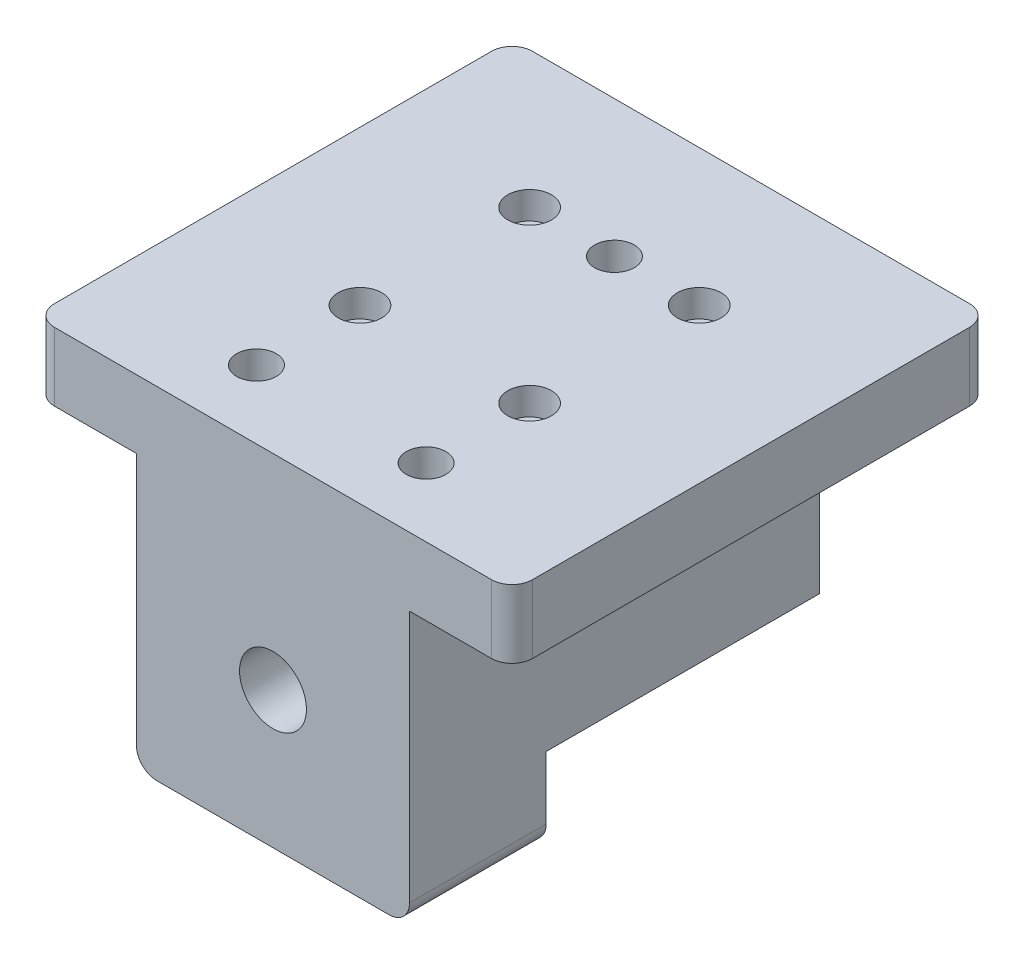
SolidWorks part; units mm, degrees
ref_plane "Front Plane" through (0, 0, 0) normal (0, 0, 1) x (1, 0, 0)
ref_plane "Top Plane" through (0, 0, 0) normal (0, 1, 0) x (1, 0, 0)
ref_plane "Right Plane" through (0, 0, 0) normal (1, 0, 0) x (0, 0, -1)
sketch "Sketch1" plane through (0, 0, 0) normal (0, 0, 1) x (1, 0, 0)
  line L0 (4.222, -2.1267) -> (4.222, 1.8147)
  line L1 (4.7961, 3.2006) -> (6.7433, 5.1479)
  line L2 (6.9512, 5.234) -> (8.142, 5.234)
  line L3 (8.436, 4.94) -> (8.436, 3.176)
  line L4 (8.73, 2.882) -> (9.416, 2.882)
  line L5 (9.71, 3.176) -> (9.71, 3.528)
  line L6 (9.71, 3.528) -> (9.906, 3.528)
  line L7 (10.2, 3.822) -> (10.2, 8.052)
  line L8 (8.608, 9.922) -> (4.1, 9.922)
  line L9 (3.806, 9.628) -> (3.806, 9.432)
  line L10 (3.806, 9.432) -> (3.454, 9.432)
  line L11 (3.16, 9.138) -> (3.16, 8.452)
  line L12 (3.454, 8.158) -> (5.218, 8.158)
  line L13 (5.512, 7.864) -> (5.512, 6.6732)
  line L14 (5.4259, 6.4653) -> (3.4786, 4.5181)
  line L15 (2.0927, 3.944) -> (-1.8487, 3.944)
  line L16 (-3.2346, 4.5181) -> (-5.1819, 6.4653)
  line L17 (-5.268, 6.6732) -> (-5.268, 7.864)
  line L18 (-4.974, 8.158) -> (-3.21, 8.158)
  line L19 (-2.916, 8.452) -> (-2.916, 9.138)
  line L20 (-3.21, 9.432) -> (-3.406, 9.432)
  line L21 (-3.406, 9.432) -> (-3.406, 9.628)
  line L22 (-3.7, 9.922) -> (-8.33, 9.922)
  line L23 (-9.8, 8.33) -> (-9.8, 3.822)
  line L24 (-9.506, 3.528) -> (-9.31, 3.528)
  line L25 (-9.31, 3.528) -> (-9.31, 3.176)
  line L26 (-9.016, 2.882) -> (-8.33, 2.882)
  line L27 (-8.036, 3.176) -> (-8.036, 4.94)
  line L28 (-7.742, 5.234) -> (-6.5512, 5.234)
  line L29 (-6.3433, 5.1479) -> (-4.3961, 3.2006)
  line L30 (-3.822, 1.8147) -> (-3.822, -2.1267)
  line L31 (-4.3961, -3.5126) -> (-6.3433, -5.4599)
  line L32 (-6.5512, -5.546) -> (-7.742, -5.546)
  line L33 (-8.036, -5.252) -> (-8.036, -3.488)
  line L34 (-8.33, -3.194) -> (-9.016, -3.194)
  line L35 (-9.31, -3.488) -> (-9.31, -3.684)
  line L36 (-9.31, -3.684) -> (-9.506, -3.684)
  line L37 (-9.8, -3.978) -> (-9.8, -8.486)
  line L38 (-8.33, -10.078) -> (-3.7, -10.078)
  line L39 (-2.916, -9.294) -> (-2.916, -8.608)
  line L40 (-3.21, -8.314) -> (-4.974, -8.314)
  line L41 (-5.268, -8.02) -> (-5.268, -6.8292)
  line L42 (-5.1819, -6.6213) -> (-3.2346, -4.6741)
  line L43 (-1.8487, -4.1) -> (2.0927, -4.1)
  line L44 (3.4786, -4.6741) -> (5.4259, -6.6213)
  line L45 (5.668, -6.8292) -> (5.668, -8.02)
  line L46 (5.374, -8.314) -> (3.61, -8.314)
  line L47 (3.316, -8.608) -> (3.316, -9.294)
  line L48 (4.1, -10.078) -> (8.608, -10.078)
  line L49 (10.2, -8.608) -> (10.2, -3.978)
  line L50 (9.906, -3.684) -> (9.71, -3.684)
  line L51 (9.71, -3.684) -> (9.71, -3.488)
  line L52 (9.416, -3.194) -> (8.73, -3.194)
  line L53 (8.436, -3.488) -> (8.436, -5.252)
  line L54 (8.142, -5.546) -> (6.8294, -5.546)
  line L55 (6.8294, -5.546) -> (4.7961, -3.5126)
  line L56 (4.1, 9.922) -> (-3.7, 9.922)
  line L57 (10.2, 3.822) -> (10.2, -3.978)
  line L58 (-9.8, 3.822) -> (-9.8, -3.978)
  line L59 (-3.7, -10.078) -> (4.1, -10.078)
  line L60 (-9.8, 8.33) -> (-9.8, 9.922)
  line L61 (-9.8, 9.922) -> (-8.33, 9.922)
  line L62 (8.608, 9.922) -> (10.2, 9.922)
  line L63 (10.2, 9.922) -> (10.2, 8.052)
  line L64 (10.2, -8.608) -> (10.2, -10.078)
  line L65 (10.2, -10.078) -> (8.608, -10.078)
  line L66 (-8.33, -10.078) -> (-9.8, -10.078)
  line L67 (-9.8, -10.078) -> (-9.8, -8.486)
  circle A0 centre (0.2, -0.078) radius 2.45
  arc A1 (4.222, -2.1267) -> (4.7961, -3.5126) centre (6.182, -2.1267) ccw
  arc A2 (4.7961, 3.2006) -> (4.222, 1.8147) centre (6.182, 1.8147) ccw
  arc A3 (6.9512, 5.234) -> (6.7433, 5.1479) centre (6.9512, 4.94) ccw
  arc A4 (8.436, 4.94) -> (8.142, 5.234) centre (8.142, 4.94) ccw
  arc A5 (8.436, 3.176) -> (8.73, 2.882) centre (8.73, 3.176) ccw
  arc A6 (9.416, 2.882) -> (9.71, 3.176) centre (9.416, 3.176) ccw
  arc A7 (9.906, 3.528) -> (10.2, 3.822) centre (9.906, 3.822) ccw
  arc A9 (4.1, 9.922) -> (3.806, 9.628) centre (4.1, 9.628) ccw
  arc A10 (3.454, 9.432) -> (3.16, 9.138) centre (3.454, 9.138) ccw
  arc A11 (3.16, 8.452) -> (3.454, 8.158) centre (3.454, 8.452) ccw
  arc A12 (5.512, 7.864) -> (5.218, 8.158) centre (5.218, 7.864) ccw
  arc A13 (5.4259, 6.4653) -> (5.512, 6.6732) centre (5.218, 6.6732) ccw
  arc A14 (2.0927, 3.944) -> (3.4786, 4.5181) centre (2.0927, 5.904) ccw
  arc A15 (-3.2346, 4.5181) -> (-1.8487, 3.944) centre (-1.8487, 5.904) ccw
  arc A16 (-5.268, 6.6732) -> (-5.1819, 6.4653) centre (-4.974, 6.6732) ccw
  arc A17 (-4.974, 8.158) -> (-5.268, 7.864) centre (-4.974, 7.864) ccw
  arc A18 (-3.21, 8.158) -> (-2.916, 8.452) centre (-3.21, 8.452) ccw
  arc A19 (-2.916, 9.138) -> (-3.21, 9.432) centre (-3.21, 9.138) ccw
  arc A20 (-3.406, 9.628) -> (-3.7, 9.922) centre (-3.7, 9.628) ccw
  arc A22 (-9.8, 3.822) -> (-9.506, 3.528) centre (-9.506, 3.822) ccw
  arc A23 (-9.31, 3.176) -> (-9.016, 2.882) centre (-9.016, 3.176) ccw
  arc A24 (-8.33, 2.882) -> (-8.036, 3.176) centre (-8.33, 3.176) ccw
  arc A25 (-7.742, 5.234) -> (-8.036, 4.94) centre (-7.742, 4.94) ccw
  arc A26 (-6.3433, 5.1479) -> (-6.5512, 5.234) centre (-6.5512, 4.94) ccw
  arc A27 (-3.822, 1.8147) -> (-4.3961, 3.2006) centre (-5.782, 1.8147) ccw
  arc A28 (-4.3961, -3.5126) -> (-3.822, -2.1267) centre (-5.782, -2.1267) ccw
  arc A29 (-6.5512, -5.546) -> (-6.3433, -5.4599) centre (-6.5512, -5.252) ccw
  arc A30 (-8.036, -5.252) -> (-7.742, -5.546) centre (-7.742, -5.252) ccw
  arc A31 (-8.036, -3.488) -> (-8.33, -3.194) centre (-8.33, -3.488) ccw
  arc A32 (-9.016, -3.194) -> (-9.31, -3.488) centre (-9.016, -3.488) ccw
  arc A33 (-9.506, -3.684) -> (-9.8, -3.978) centre (-9.506, -3.978) ccw
  arc A35 (-3.7, -10.078) -> (-3.406, -9.784) centre (-3.7, -9.784) ccw
  arc A36 (-3.21, -9.588) -> (-3.406, -9.784) centre (-3.21, -9.784) ccw
  arc A37 (-3.21, -9.588) -> (-2.916, -9.294) centre (-3.21, -9.294) ccw
  arc A38 (-2.916, -8.608) -> (-3.21, -8.314) centre (-3.21, -8.608) ccw
  arc A39 (-5.268, -8.02) -> (-4.974, -8.314) centre (-4.974, -8.02) ccw
  arc A40 (-5.1819, -6.6213) -> (-5.268, -6.8292) centre (-4.974, -6.8292) ccw
  arc A41 (-1.8487, -4.1) -> (-3.2346, -4.6741) centre (-1.8487, -6.06) ccw
  arc A42 (3.4786, -4.6741) -> (2.0927, -4.1) centre (2.0927, -6.06) ccw
  arc A43 (5.668, -6.8292) -> (5.4259, -6.6213) centre (5.3861, -6.9126) ccw
  arc A44 (5.374, -8.314) -> (5.668, -8.02) centre (5.374, -8.02) ccw
  arc A45 (3.61, -8.314) -> (3.316, -8.608) centre (3.61, -8.608) ccw
  arc A46 (3.316, -9.294) -> (3.61, -9.588) centre (3.61, -9.294) ccw
  arc A47 (3.806, -9.784) -> (3.61, -9.588) centre (3.61, -9.784) ccw
  arc A48 (3.806, -9.784) -> (4.1, -10.078) centre (4.1, -9.784) ccw
  arc A50 (10.2, -3.978) -> (9.906, -3.684) centre (9.906, -3.978) ccw
  arc A51 (9.71, -3.488) -> (9.416, -3.194) centre (9.416, -3.488) ccw
  arc A52 (8.73, -3.194) -> (8.436, -3.488) centre (8.73, -3.488) ccw
  arc A53 (8.142, -5.546) -> (8.436, -5.252) centre (8.142, -5.252) ccw
  dimension "D1" = 4.9
  dimension "D2" = 7.8
  dimension "D3" = 6.1
  dimension "D4" = 6.1
  dimension "D5" = 7.8
  dimension "D6" = 6.1
  dimension "D7" = 20
  dimension "D8" = 7.8
  dimension "D9" = 6.1
  dimension "D10" = 20
  dimension "D11" = 20
  dimension "D12" = 7.8
  dimension "D13" = 6.1
  dimension "D14" = 10
  dimension "D15" = 10
extrude "Boss-Extrude1" add sketch "Sketch1" along normal blind 10 contours A53 L54 L55 A1 L0 A2 L1 A3 L2 A4 L3 A5 L4 A6 L5 L6 A7 L7 L8 A9 L9 L10 A10 L11 A11 L12 A12 L13 A13 L14 A14 L15 A15 L16 A16 L17 A17 L18 A18 L19 A19 L20 L21 A20 L22 L23 A22 L24 L25 region at (4.1099, -2.985, 0)
extrude "Boss-Extrude2" add sketch "Sketch1<3>" along normal blind 10 and the other way blind 20 contours A20 L21 L20 A19 L19 A18 L18 A17 L17 A16 L16 A15 L15 A14 L14 A13 L13 A12 L12 A11 L11 A10 L10 L9 A9 L56 | L54 A53 L53 A52 L52 A51 L51 L50 A50 L57 A7 L6 L5 A6 L4 A5 L3 A4 L2 A3 L1 A2 L0 A1 L55 | A48 A47 A46 L47 A45 L46 A44 L45 A43 L44 A42 L43 A41 L42 A40 L41 A39 L40 A38 L39 A37 A36 A35 L59 | A33 L36 L35 A32 L34 A31 L33 A30 L32 A29 L31 A28 L30 A27 L29 A26 L28 A25 L27 A24 L26 A23 L25 L24 A22 L58 region at (7.1936, -0.1506, 0) region at (0.1676, -7.0804, 0) region at (0.1276, 6.9156, 0) region at (-6.7936, -0.1504, 0)
sketch "Sketch1<3>" plane through (0, 0, 0) normal (0, 0, 1) x (1, 0, 0) same geometry as "Sketch1"
sketch "Sketch7" plane through (0, 9.922, 0) normal (0, 1, 0) x (1, 0, 0)
  line L0 (-17.3, -10) -> (-17.3, 25)
  line L1 (-17.3, 25) -> (17.7, 25)
  line L2 (17.7, 25) -> (17.7, -10)
  line L3 (-9.8, -10) -> (10.2, -10) construction
  line L4 (10.2, -10) -> (10.2, 0) construction
  line L18 (-17.3, -10) -> (17.7, -10)
  dimension "D2" = 7.5
  dimension "D3" = 35
  dimension "D1" = 35
extrude "Boss-Extrude10" add sketch "Sketch7" along normal blind 5
sketch "Sketch9" plane through (0, 14.922, 0) normal (0, 1, 0) x (1, 0, 0)
  line L0 (17.7, -10) -> (17.7, 25) construction
  line L1 (17.7, 25) -> (-17.3, 25) construction
  circle A0 centre (6.41, 15) radius 1.6
  circle A1 centre (-6.01, 15) radius 1.6
  circle A2 centre (-6.01, 2.58) radius 1.6
  circle A3 centre (6.41, 2.58) radius 1.6
  dimension "D1" = 3.2
  dimension "D2" = 12.42
  dimension "D3" = 12.42
  dimension "D4" = 12.42
  dimension "D5" = 12.42
  dimension "D6" = 11.29
  dimension "D7" = 10
extrude "Cut-Extrude1" cut sketch "Sketch9" against normal blind 2
sketch "Sketch12" plane through (0, 14.922, 0) normal (0, 1, 0) x (1, 0, 0)
  line L0 (-17.3, -10) -> (17.7, -10) construction
  line L1 (17.7, 25) -> (-17.3, 25) construction
  line L2 (17.7, -10) -> (17.7, 25) construction
  line L5 (-17.3, 25) -> (-17.3, -10) construction
  circle A2 centre (0.2, 15) radius 1.45
  circle A3 centre (-6.01, -5) radius 1.45
  circle A4 centre (6.41, -5) radius 1.45
  point P5 (-6.01, 15)
  dimension "D4" = 10
  dimension "D5" = 5
  dimension "D1" = 12.42
  dimension "D3" = 2.9
  dimension "D2" = 11.29
  dimension "D6" = 17.5
extrude "Cut-Extrude2" cut sketch "Sketch12" against normal through all
fillet "Fillet3" radius 1.5 6 edges at (10.2, -10.078, 5) (-9.8, -10.078, 5) (-17.3, 12.422, -25) (-17.3, 12.422, 10) (17.7, 12.422, -25) (17.7, 12.422, 10)
